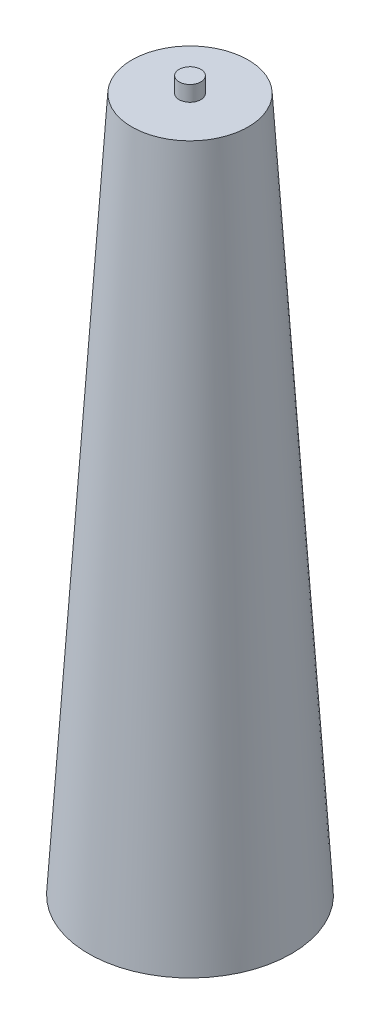
SolidWorks part; units mm, degrees
material "S-Glass Fiber"
ref_plane "Front Plane" through (0, 0, 0) normal (0, 0, 1) x (1, 0, 0)
ref_plane "Top Plane" through (0, 0, 0) normal (0, 1, 0) x (1, 0, 0)
ref_plane "Right Plane" through (0, 0, 0) normal (1, 0, 0) x (0, 0, -1)
sketch "Sketch1" plane through (0, 0, 0) normal (0, 0, 1) x (1, 0, 0)
  line L0 (0, 0) -> (-33.401, 0)
  line L1 (-33.401, 0) -> (-19.1389, 228.6)
  line L2 (-19.1389, 228.6) -> (0, 228.6)
  line L3 (0, 228.6) -> (0, 0)
  dimension "D1" = 33.401
  dimension "D2" = 3.57
  dimension "D3" = 228.6
revolve "Revolve1" add sketch "Sketch1" angle 360 about L3
sketch "Sketch2" plane through (0, 228.6, 0) normal (0, 1, 0) x (1, 0, 0)
  circle A0 centre (0, 0) radius 3.5814
  dimension "D1" = 7.1628
extrude "Boss-Extrude1" add sketch "Sketch2" along normal blind 5.08
sketch "Sketch3" plane through (0, 0, 0) normal (0, -1, 0) x (1, 0, 0)
  circle A0 centre (0, 0) radius 3.5814
  dimension "D1" = 7.1628
extrude "Cut-Extrude1" cut sketch "Sketch3" against normal blind 5.08
shell "Shell3" thickness 2.54
